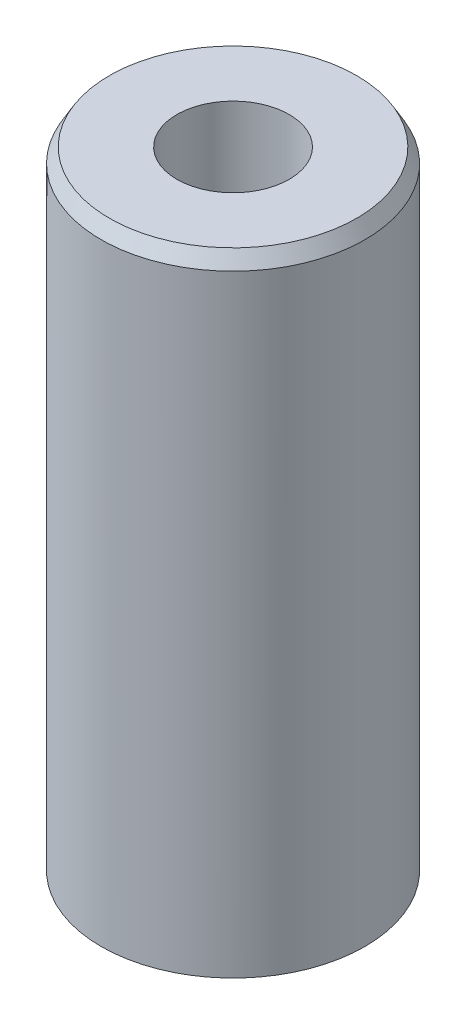
SolidWorks part; units mm, degrees
ref_plane "Front Plane" through (0, 0, 0) normal (0, 0, 1) x (1, 0, 0)
ref_plane "Top Plane" through (0, 0, 0) normal (0, 1, 0) x (1, 0, 0)
ref_plane "Right Plane" through (0, 0, 0) normal (1, 0, 0) x (0, 0, -1)
sketch "Sketch1" plane through (0, 0, 0) normal (0, 1, 0) x (1, 0, 0)
  circle A0 centre (0, 0) radius 50
  dimension "SHAFT_OD" = 100
extrude "Boss-Extrude1" add sketch "Sketch1" along normal blind 240.6123
sketch "Sketch2" plane through (0, 0, 0) normal (0, 1, 0) x (1, 0, 0)
  circle A0 centre (0, 0) radius 21.2913
  dimension "BORE_D" = 42.5826
extrude "Cut-Extrude1" cut sketch "Sketch2" along normal through all
chamfer "Chamfer1" distance 5.4501 angle 30 2 edges at (0, 240.6123, 50) (0, 0, 50) first distance on face at (0, 240.6123, 50) first distance on face at (0, 0, 21.2913)
